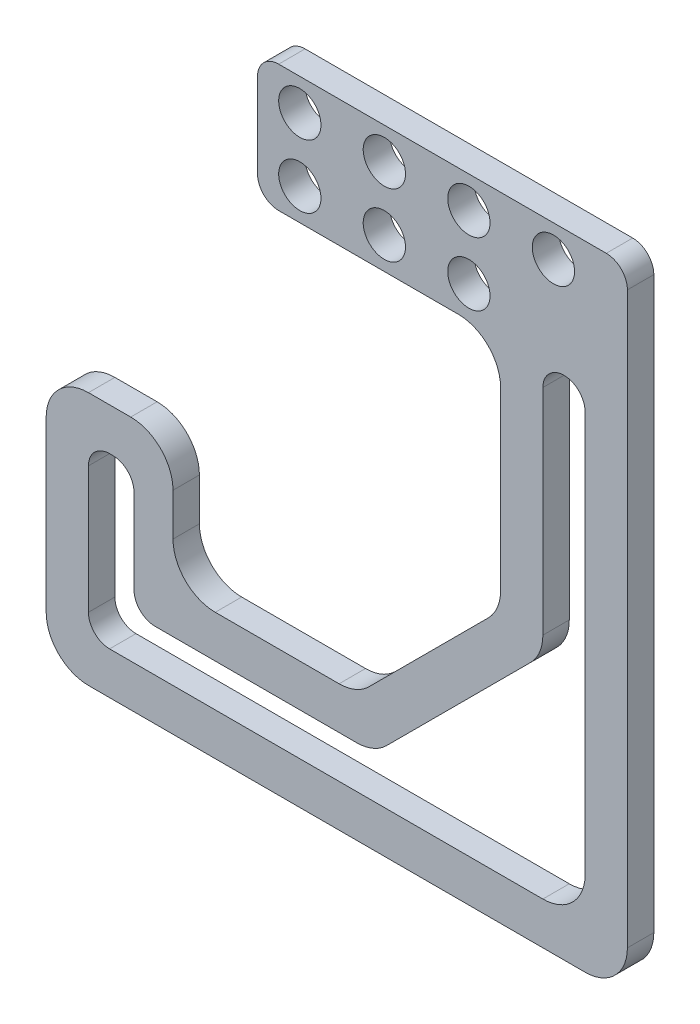
SolidWorks part; units mm, degrees
ref_plane "Front Plane" through (0, 0, 0) normal (0, 0, 1) x (1, 0, 0)
ref_plane "Top Plane" through (0, 0, 0) normal (0, 1, 0) x (1, 0, 0)
ref_plane "Right Plane" through (0, 0, 0) normal (1, 0, 0) x (0, 0, -1)
sketch "Sketch1" plane through (0, 0, 0) normal (0, 1, 0) x (1, 0, 0)
  line L1 (43.9941, 0) -> (21.997, 38.1) construction
  line L2 (21.997, 38.1) -> (-21.997, 38.1) construction
  line L3 (-21.997, 38.1) -> (-43.9941, 0) construction
  line L4 (-43.9941, 0) -> (-21.997, -38.1) construction
  line L5 (-21.997, -38.1) -> (21.997, -38.1) construction
  line L6 (21.997, -38.1) -> (43.9941, 0) construction
  circle A0 centre (0, 0) radius 38.1 construction
  dimension "D1" = 76.2
ref_plane "Plane1" through (0, 0, 38.1) normal (0, 0, 1) x (1, 0, 0)
sketch "Sketch2" plane through (0, 0, 38.1) normal (0, 0, 1) x (1, 0, 0)
  line L0 (-27.5, 0) -> (27.5, 0)
  line L5 (43.9941, 0) -> (21.997, 0) construction
  line L6 (-27.5, 0) -> (-27.5, 12)
  line L7 (-15.5, 12) -> (1.8762, 12)
  line L8 (27.5, 0) -> (27.5, 59.9206)
  line L9 (15.5, 25.6238) -> (15.5, 47.9206)
  line L10 (15.5, 25.6238) -> (1.8762, 12)
  line L16 (15.5, 47.9206) -> (-7.5, 47.9206)
  line L17 (-7.5, 47.9206) -> (-7.5, 59.9206)
  line L18 (-7.5, 59.9206) -> (27.5, 59.9206)
  line L19 (23.5, 4) -> (23.5, 47.9206)
  line L23 (19.5, 23.9669) -> (19.5, 47.9206)
  line L24 (19.5, 23.9669) -> (3.5331, 8)
  line L25 (-19.1907, 8) -> (3.5331, 8)
  line L26 (-23.5, 4) -> (-23.5, 8)
  line L27 (-23.5, 4) -> (23.5, 4)
  line L28 (19.5, 47.9206) -> (23.5, 47.9206)
  line L29 (19.5, 23.9669) -> (19.5, 51.9206) construction
  line L30 (-3.5, 55.9206) -> (23.5, 55.9206) construction
  line L31 (19.5, 51.9206) -> (-3.5, 51.9206) construction
  line L32 (23.5, 4) -> (23.5, 55.9206) construction
  line L33 (-3.5, 51.9206) -> (-3.5, 55.9206) construction
  line L34 (-3.5, 56.9206) -> (20.5, 56.9206) construction
  line L35 (-27.5, 12) -> (-27.5, 24)
  line L36 (-15.5, 12) -> (-15.5, 24)
  line L37 (-27.5, 24) -> (-15.5, 24)
  line L38 (-27.5, 12) -> (1.8762, 12) construction
  line L39 (-23.5, 8) -> (-23.5, 20)
  line L40 (-23.5, 20) -> (-19.1907, 20)
  line L41 (-19.1907, 20) -> (-19.1907, 8)
  line L42 (-23.5, 8) -> (3.5331, 8) construction
  circle A0 centre (-3.5, 56.9206) radius 2
  circle A1 centre (-3.5, 50.9206) radius 2
  circle A2 centre (4.5, 50.9206) radius 2
  circle A3 centre (12.5, 50.9206) radius 2
  circle A4 centre (4.5, 56.9206) radius 2
  circle A5 centre (12.5, 56.9206) radius 2
  circle A6 centre (20.5, 56.9206) radius 2
  point P3 (0, 0)
  point P45 (0, 0)
  dimension "D6" = 4
  dimension "D1" = 27.5
  dimension "D2" = 12
  dimension "D3" = 12
  dimension "D4" = 135
  dimension "D5" = 4
  dimension "D7" = 3
  dimension "D8" = 12
  dimension "D9" = 35
  dimension "D10" = 4
  dimension "D11" = 3
  dimension "D12" = 8
  dimension "D13" = 3
  dimension "D14" = 8
  dimension "D15" = 8
  dimension "D16" = 8
  dimension "D17" = 8
  dimension "D18" = 4
  dimension "D19" = 3
  dimension "D20" = 12
  dimension "D21" = 12
  dimension "D22" = 4
extrude "Boss-Extrude1" add sketch "Sketch2" along normal blind 2.5
fillet "Fillet1" radius 4 11 edges at (19.5, 23.9669, 39.35) (3.5331, 8, 39.35) (15.5, 47.9206, 39.35) (15.5, 25.6238, 39.35) (1.8762, 12, 39.35) (-27.5, 0, 39.35) (27.5, 0, 39.35) (23.5, 4, 39.35) (-15.5, 12, 39.35) (-15.5, 24, 39.35) (-27.5, 24, 39.35)
fillet "Fillet2" radius 2 9 edges at (23.5, 47.9206, 39.35) (19.5, 47.9206, 39.35) (-23.5, 4, 39.35) (27.5, 59.9206, 39.35) (-7.5, 47.9206, 39.35) (-7.5, 59.9206, 39.35) (-19.1907, 20, 39.35) (-23.5, 20, 39.35) (-19.1907, 8, 39.35)
equation "\"pocket\"= 4mm"
